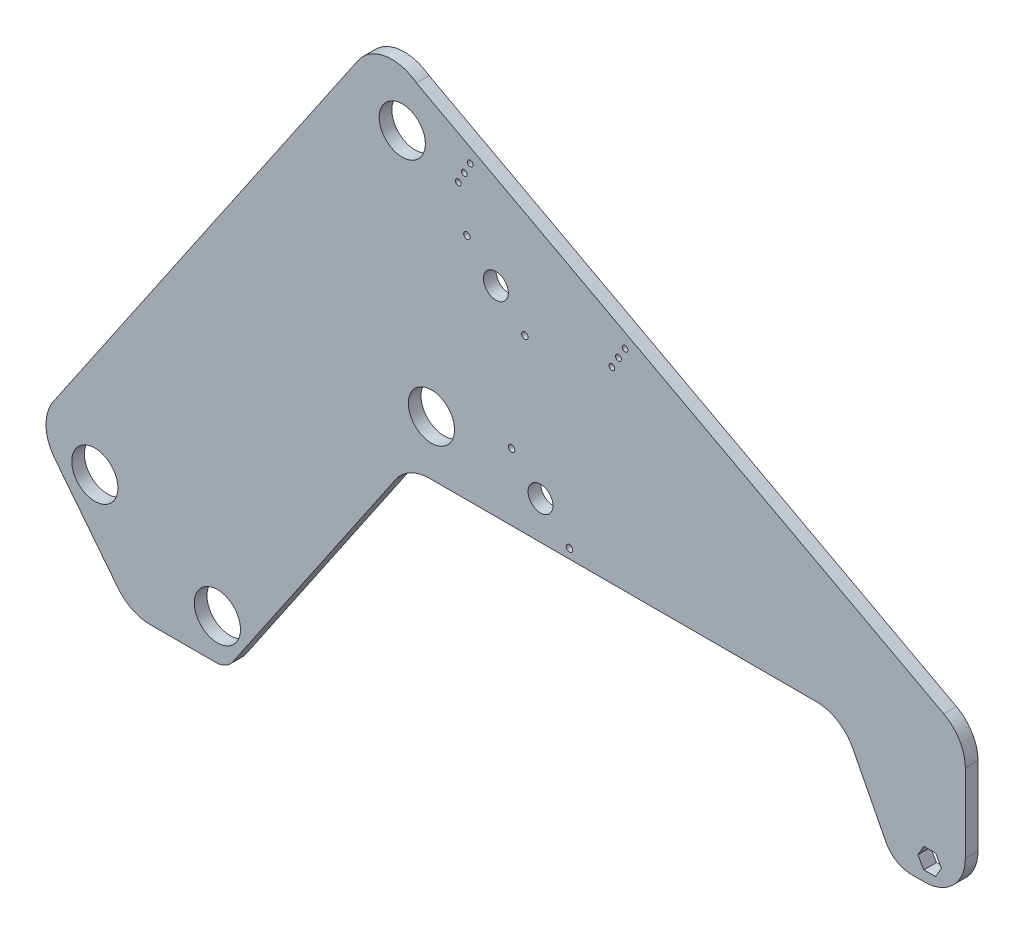
SolidWorks part; units mm, degrees
other "Markup1"
sketch "Sketch1" plane through (-441.7893, 331.8239, 6.35) normal (-0.0431, 0.0102, 0.999) x (0.9985, 0.0354, 0.0427)
sketch "Sketch2" plane through (-413.6701, 343.933, 6.35) normal (-0.0431, 0.0102, 0.999) x (0.9985, 0.0354, 0.0427)
sketch "Sketch3" plane through (-436.3774, 318.5567, 6.35) normal (-0.0431, 0.0102, 0.999) x (0.9985, 0.0354, 0.0427)
sketch "Sketch5" plane through (-436.3774, 318.5567, 6.35) normal (-0.0431, 0.0102, 0.999) x (0.9985, 0.0354, 0.0427)
sketch "Sketch7" plane through (-430.3226, 318.5567, 6.35) normal (-0.0431, 0.0102, 0.999) x (0.9985, 0.0354, 0.0427)
sketch "Sketch9" plane through (-430.3226, 318.5567, 6.35) normal (-0.0431, 0.0102, 0.999) x (0.9985, 0.0354, 0.0427)
sketch "Sketch11" plane through (-430.3226, 318.5567, 6.35) normal (-0.0431, 0.0102, 0.999) x (0.9985, 0.0354, 0.0427)
sketch "Sketch13" plane through (-430.3226, 318.5567, 6.35) normal (-0.0431, 0.0102, 0.999) x (0.9985, 0.0354, 0.0427)
other "Markup2"
sketch "Sketch4" plane through (102.4721, 318.5567, 6.35) normal (0.9364, 0.1073, 0.3342) x (0.3416, -0.0598, -0.9379)
sketch "Sketch6" plane through (102.4721, 318.5567, 6.35) normal (0.9364, 0.1073, 0.3342) x (0.3416, -0.0598, -0.9379)
sketch "Sketch8" plane through (141.2086, 318.5567, 6.35) normal (0.9364, 0.1073, 0.3342) x (0.3416, -0.0598, -0.9379)
sketch "Sketch10" plane through (141.2086, 318.5567, 6.35) normal (0.9364, 0.1073, 0.3342) x (0.3416, -0.0598, -0.9379)
sketch "Sketch12" plane through (141.2086, 318.5567, 6.35) normal (0.9364, 0.1073, 0.3342) x (0.3416, -0.0598, -0.9379)
sketch "Sketch14" plane through (141.2086, 318.5567, 6.35) normal (0.9364, 0.1073, 0.3342) x (0.3416, -0.0598, -0.9379)
material "Lexan"
ref_plane "Front Plane" through (0, 0, 0) normal (0, 0, 1) x (1, 0, 0)
ref_plane "Top Plane" through (0, 0, 0) normal (0, 1, 0) x (1, 0, 0)
ref_plane "Right Plane" through (0, 0, 0) normal (1, 0, 0) x (0, 0, -1)
sketch "Model" plane through (0, 0, 0) normal (0, 0, 1) x (1, 0, 0)
  line L1 (-191.9011, 104.6502) -> (-112.96, 104.6502)
  line L3 (-314.2383, -55.3595) -> (-212.8994, 93.5413)
  line L4 (-236.3088, 307.4396) -> (-425.9253, 28.8296)
  line L5 (-424.901, -1.1522) -> (-385.5815, -51.2048)
  line L13 (126.3831, 53.8502) -> (122.717, 60.2002)
  line L14 (122.717, 60.2002) -> (115.3846, 60.2002)
  line L15 (115.3846, 60.2002) -> (111.7185, 53.8502)
  line L16 (111.7185, 53.8502) -> (115.3846, 47.5002)
  line L17 (115.3846, 47.5002) -> (122.717, 47.5002)
  line L18 (122.717, 47.5002) -> (126.3831, 53.8502)
  line L19 (-365.6075, -60.914) -> (-324.7375, -60.914)
  line L20 (-871.0211, -88.854) -> (370.1019, -88.854) construction
  line L22 (141.2086, 66.5502) -> (141.2086, 78.8846)
  line L27 (107.6196, 41.1502) -> (115.8086, 41.1502)
  line L28 (-399.9752, 2.586) -> (-323.7752, -35.514) construction
  line L29 (-323.7752, -35.514) -> (-190.7071, 138.5169) construction
  line L30 (-190.7071, 138.5169) -> (-208.8329, 283.4378) construction
  line L31 (-208.8329, 283.4378) -> (-399.9752, 2.586) construction
  line L32 (91.8004, 50.8135) -> (71.26, 90.8456)
  line L33 (48.6612, 104.6502) -> (-11.3966, 104.6502)
  line L34 (141.2086, 78.8846) -> (141.2086, 115.3033)
  line L35 (127.8091, 137.6897) -> (-86.3327, 252.4836)
  line L36 (-168.6493, 244.9512) -> (-132.6215, 244.9512) construction
  line L37 (-132.6215, 244.9512) -> (-132.6215, 209.1372)
  line L38 (-168.6493, 244.9512) -> (-132.6215, 209.1372)
  line L39 (-168.6493, 244.9512) -> (-150.6354, 244.9512)
  line L40 (-68.51, 104.6502) -> (-2.1388, 104.6502)
  line L41 (-122.3008, 271.7648) -> (-200.0053, 313.4195)
  line L42 (-122.3008, 271.7648) -> (-86.3327, 252.4836)
  line L43 (-112.96, 104.6502) -> (-68.51, 104.6502)
  line L44 (-150.6354, 244.9512) -> (-150.6354, 228.9492)
  line L45 (-140.9024, 144.2514) -> (-104.8747, 144.2514) construction
  line L46 (-104.8747, 144.2514) -> (-104.8747, 108.4374)
  line L47 (-140.9024, 144.2514) -> (-104.8747, 108.4374)
  line L48 (-140.9024, 144.2514) -> (-122.8885, 144.2514)
  line L49 (-122.8885, 144.2514) -> (-122.8885, 128.2494)
  line L50 (-200.0053, 313.4195) -> (-69.4423, 236.8008)
  line L51 (-69.4423, 236.8008) -> (-66.6822, 241.9496)
  line L52 (-71.7813, 232.7907) -> (-69.4423, 236.8008)
  line L53 (-200.0053, 313.4195) -> (-165.7365, 288.4207)
  line L54 (-165.7365, 288.4207) -> (-162.9764, 293.5696)
  line L55 (-165.7365, 288.4207) -> (-169.7157, 280.9976)
  line L56 (-166.5765, 286.8537) -> (-170.2967, 279.9139) construction
  arc A3 (121.2475, 59.8082) -> (121.352, 60.2002) centre (96.7586, 66.5502) ccw
  circle A9 centre (-323.7752, -35.514) radius 14.351
  circle A10 centre (-399.9752, 2.586) radius 14.351
  circle A12 centre (-190.7071, 138.5169) radius 14.351
  arc A15 (107.6196, 41.1502) -> (91.8004, 50.8135) centre (107.6196, 58.9302) cw
  arc A21 (-191.9011, 104.6502) -> (-212.8994, 93.5413) centre (-191.9011, 79.2502) ccw
  circle A22 centre (-208.8329, 283.4378) radius 14.351
  circle A24 centre (119.0508, 53.8502) radius 6.35 construction
  arc A31 (-324.7375, -60.914) -> (-314.2383, -55.3595) centre (-324.7375, -48.214) ccw
  arc A40 (114.7422, 48.6129) -> (115.0458, 48.9225) centre (96.7586, 66.5502) ccw
  arc A43 (115.8086, 41.1502) -> (141.2086, 66.5502) centre (115.8086, 66.5502) ccw
  arc A44 (-236.3088, 307.4396) -> (-200.0053, 313.4195) centre (-215.3105, 293.1486) cw
  arc A45 (-365.6075, -60.914) -> (-385.5815, -51.2048) centre (-365.6075, -35.514) cw
  arc A46 (71.26, 90.8456) -> (48.6612, 104.6502) centre (48.6612, 79.2502) ccw
  arc A47 (141.2086, 115.3033) -> (127.8091, 137.6897) centre (115.8086, 115.3033) ccw
  arc A48 (-424.901, -1.1522) -> (-425.9253, 28.8296) centre (-404.9271, 14.5386) cw
  circle A51 centre (-168.6493, 246.9832) radius 2.032
  circle A52 centre (-132.6215, 211.1692) radius 2.032
  circle A53 centre (-150.6354, 228.9492) radius 7.747
  circle A54 centre (-140.9024, 146.2834) radius 2.032
  circle A55 centre (-104.8747, 110.4694) radius 2.032
  circle A56 centre (-122.8885, 128.2494) radius 7.747
  circle A57 centre (-70.3381, 235.265) radius 1.778
  circle A60 centre (-74.4334, 228.2441) radius 1.778
  circle A61 centre (-78.5287, 221.2232) radius 1.778
  circle A62 centre (-166.5765, 286.8537) radius 1.778
  circle A63 centre (-170.2967, 279.9139) radius 1.778
  circle A64 centre (-174.0168, 272.9742) radius 1.778
  ellipse E0 centre (-551.1692, 173.9527) end of major axis (-591.2054, 216.0961) minor radius 17.278
  point P31 (-177.5612, 330.9695)
  point P34 (100.2935, -12.8222)
  point P43 (-377.9543, -60.914)
  point P55 (96.7586, 41.1502)
  point P59 (174.831, 53.8502)
  point P60 (-205.3388, 104.6502)
  point P64 (-436.3829, 13.4639)
  point P105 (-168.6493, 244.9512)
  point P113 (-149.9754, 242.649)
  dimension "D3" = 38.1
  dimension "D4" = 104.6502
  dimension "D5" = 76.2
  dimension "D6" = 44.45
  dimension "D7" = 12.7
  dimension "D8" = 28.702
  dimension "D11" = 139.7
  dimension "D12" = 27.94
  dimension "D21" = 124.238
  dimension "D13" = 12.7
  dimension "D16" = 355.6
  dimension "D23" = 25.4
  dimension "D24" = 25.4
  dimension "D26" = 25.4
  dimension "D14" = 406.4
  dimension "D20" = 254
  dimension "D29" = 25.4
  dimension "D31" = 25.4
  dimension "D25" = 88.9
  dimension "D30" = 17.78
  dimension "D32" = 25.4
  dimension "D33" = 25.4
  dimension "D34" = 35.814
  dimension "D35" = 50.8
  dimension "D37" = 4.064
  dimension "D38" = 4.064
  dimension "D39" = 15.494
  dimension "D42" = 4.064
  dimension "D43" = 15.494
  dimension "D44" = 4.064
  dimension "D48" = 3.556
  dimension "D52" = 3.556
  dimension "D9" = 19.05
  dimension "D10" = 146.05
  dimension "D15" = 33.8667
  dimension "D17" = 339.725
  dimension "D18" = 219.075
  dimension "D19" = 50.8
  dimension "D22" = 25.4
  dimension "D27" = 53.2168
  dimension "D28" = 12.7
  dimension "D36" = 16.002
  dimension "D40" = 35.814
  dimension "D41" = 16.002
  dimension "D45" = 50.8
  dimension "D46" = 151.384
  dimension "D47" = 5.842
  dimension "D50" = 42.418
  dimension "D51" = 5.842
  dimension "D54" = 7.874
  dimension "D49" = 3
  dimension "D53" = 3
extrude "Boss-Extrude1" add sketch "Model" along normal blind 7.874 contours A48 L5 A45 L19 A31 L3 A21 L1 L43 L40 L33 A46 L32 A15 L27 A43 L22 L34 A47 L35 L42 L41 A44 L4 A56 L47 A54 L48 L49 A55 A53 L38 A51 L39 L44 A52 | A56 L49 L48 L47 | A53 L44 L39 L38 | L50 L51 L42 L41 | L53 L54 L50 | L50 L54 L41 region at (-206.9871, 107.7659, 0) region at (-175.5748, 299.7095, 0) region at (-176.4949, 297.9932, 0) region at (-106.7329, 261.0765, 0) region at (-157.6741, 240.7127, 0) region at (-129.9272, 140.0129, 0)
